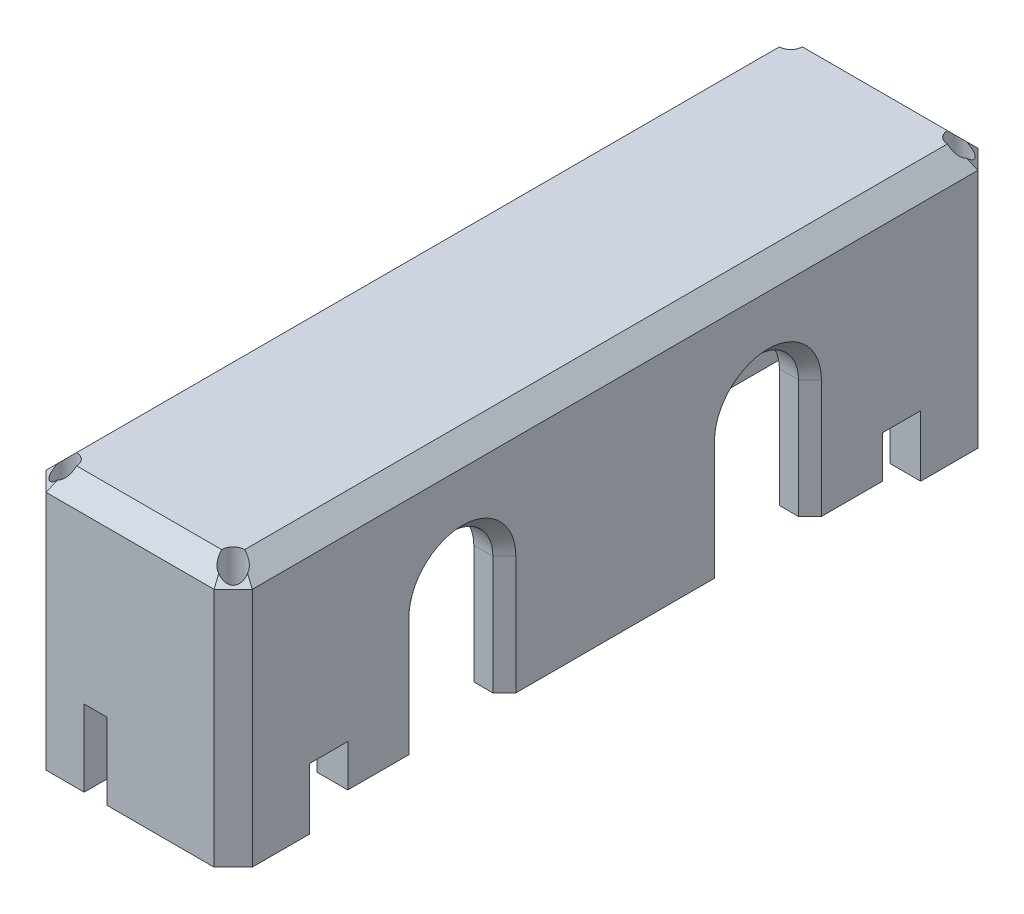
SolidWorks part; units mm, degrees
ref_plane "Płaszczyzna przednia" through (0, 0, 0) normal (0, 0, 1) x (1, 0, 0)
ref_plane "Płaszczyzna górna" through (0, 0, 0) normal (0, 1, 0) x (1, 0, 0)
ref_plane "Płaszczyzna prawa" through (0, 0, 0) normal (1, 0, 0) x (0, 0, -1)
sketch "Sketch2" plane through (0, 0, 0) normal (0, 1, 0) x (1, 0, 0)
  line L5 (27, -100) -> (-27, -100)
  line L6 (27, -100) -> (27, 100)
  line L11 (27, 100) -> (-27, 100)
  line L12 (-27, -100) -> (-27, 100)
  line L13 (27, -100) -> (-27, 100) construction
  line L14 (27, 100) -> (-27, -100) construction
  line L15 (19, -92) -> (-19, -92)
  line L16 (19, -92) -> (19, 92)
  line L17 (19, 92) -> (-19, 92)
  line L18 (-19, -92) -> (-19, 92)
  line L19 (19, -92) -> (-19, 92) construction
  line L20 (19, 92) -> (-19, -92) construction
  point P0 (0, 0)
  point P6 (0, 0)
  dimension "D1" = 8
  dimension "D2" = 8
  dimension "D3" = 200
  dimension "D4" = 54
extrude "Boss-Extrude2" add sketch "Sketch2" along normal blind 55
sketch "Sketch3" plane through (0, 0, 0) normal (1, 0, 0) x (0, 0, -1)
  line L0 (-40, 55) -> (-40, 0) construction
  line L1 (-100, 0) -> (100, 0) construction
  line L6 (-51, 0) -> (-51, 31)
  line L7 (-29, 0) -> (-29, 31)
  line L8 (-51, 0) -> (-29, 0)
  line L9 (0, 29.7) -> (0, -29.7) construction
  line L10 (51, 0) -> (51, 31)
  line L11 (29, 0) -> (29, 31)
  line L12 (51, 0) -> (29, 0)
  line L13 (-100, 55) -> (-100, 0) construction
  arc A0 (-51, 31) -> (-29, 31) centre (-40, 31) cw
  arc A1 (51, 31) -> (29, 31) centre (40, 31) ccw
  dimension "D1" = 60
  dimension "D3" = 11
  dimension "D4" = 31
extrude "Cut-Extrude1" cut sketch "Sketch3" along normal through all
sketch "Sketch5" plane through (0, 0, 0) normal (0, 1, 0) x (1, 0, 0)
  line L1 (27, 100) -> (-27, 100)
  line L2 (27, 100) -> (27, -100)
  line L3 (27, -100) -> (-27, -100)
  line L4 (-27, 100) -> (-27, -100)
  line L5 (27, 100) -> (-27, -100) construction
  line L6 (27, -100) -> (-27, 100) construction
  point P0 (0, 0)
extrude "Boss-Extrude3" add sketch "Sketch5" along normal blind 8 from surface starting at face at (0, 55, 0)
sketch "Sketch6" plane through (0, 0, 0) normal (0, 1, 0) x (1, 0, 0)
  line L1 (22, -95) -> (-22, -95) construction
  line L2 (22, -95) -> (22, 95) construction
  line L3 (22, 95) -> (-22, 95) construction
  line L4 (-22, -95) -> (-22, 95) construction
  line L5 (22, -95) -> (-22, 95) construction
  line L6 (22, 95) -> (-22, -95) construction
  line L7 (-27, -100) -> (27, -100) construction
  line L9 (-27, 100) -> (-27, -100) construction
  circle A0 centre (22, -95) radius 1.75
  circle A1 centre (-22, -95) radius 1.75
  circle A2 centre (-22, 95) radius 1.75
  circle A3 centre (22, 95) radius 1.75
  point P0 (0, 0)
  dimension "D3" = 3.5
  dimension "D1" = 5
  dimension "D2" = 5
extrude "Cut-Extrude2" cut sketch "Sketch6" along normal through all both and the other way through all
sketch "Sketch7" plane through (0, 0, 0) normal (0, 1, 0) x (1, 0, 0)
  circle A0 centre (-22, -95) radius 3
  circle A1 centre (-22, 95) radius 3
  circle A2 centre (22, 95) radius 3
  circle A3 centre (22, -95) radius 3
  dimension "D1" = 6
extrude "Cut-Extrude3" cut sketch "Sketch7" against normal blind 44 from surface starting at face at (22, 63, -93.25)
chamfer "Chamfer1" distance 5 angle 45 4 edges at (-27, 31.5, 100) (-27, 31.5, -100) (27, 31.5, -100) (27, 31.5, 100)
chamfer "Chamfer3" distance 5 angle 45 8 edges at (27, 63, 0) (24.5, 63, 97.5) (0, 63, 100) (-24.5, 63, 97.5) (-27, 63, 0) (-24.5, 63, -97.5) (0, 63, -100) (24.5, 63, -97.5)
chamfer "Chamfer4" distance 3 angle 45 6 edges at (27, 15.5, -29) (27, 42, -40) (27, 15.5, -51) (27, 15.5, 51) (27, 42, 40) (27, 15.5, 29)
sketch "Sketch8" plane through (0, 0, 0) normal (0, 1, 0) x (1, 0, 0)
  line L0 (27, -70) -> (19, -70)
  line L1 (27, -95) -> (27, -54) construction
  line L2 (19, -92) -> (19, 92) construction
  line L3 (19, -70) -> (19, -92)
  line L4 (19, -92) -> (-19, -92)
  line L5 (-19, -92) -> (-19, -70)
  line L6 (-19, 92) -> (-19, -92) construction
  line L7 (-19, -70) -> (-27, -70)
  line L8 (-27, 95) -> (-27, -95) construction
  line L9 (-27, -70) -> (-27, -95)
  line L10 (-27, -95) -> (-22, -100)
  line L11 (-22, -100) -> (22, -100)
  line L12 (22, -100) -> (27, -95)
  line L13 (27, -95) -> (27, -70)
  line L14 (-29.7, 0) -> (29.7, 0) construction
  line L15 (27, 95) -> (27, 70)
  line L16 (22, 100) -> (27, 95)
  line L17 (-22, 100) -> (22, 100)
  line L18 (-27, 95) -> (-22, 100)
  line L19 (-27, 70) -> (-27, 95)
  line L20 (-19, 70) -> (-27, 70)
  line L21 (-19, 92) -> (-19, 70)
  line L22 (19, 92) -> (-19, 92)
  line L23 (19, 70) -> (19, 92)
  line L24 (27, 70) -> (19, 70)
  circle A0 centre (22, -95) radius 1.75
  circle A1 centre (-22, -95) radius 1.75
  circle A2 centre (-22, 95) radius 1.75
  circle A3 centre (22, 95) radius 1.75
  dimension "D1" = 30
extrude "Boss-Extrude4" add sketch "Sketch8" against normal blind 5
sketch "Sketch9" plane through (0, 0, 0) normal (0, 0, 1) x (1, 0, 0)
  line L1 (-6, -5) -> (-12, -5)
  line L2 (-6, -5) -> (-6, 15)
  line L3 (-6, 15) -> (-12, 15)
  line L4 (-12, -5) -> (-12, 15)
  line L5 (-6, -5) -> (-12, 15) construction
  line L6 (-6, 15) -> (-12, -5) construction
  line L7 (-22, -5) -> (22, -5) construction
  point P0 (-9, 5)
  dimension "D1" = 20
  dimension "D2" = 6
  dimension "D3" = 6
extrude "Cut-Extrude4" cut sketch "Sketch9" against normal through all both and the other way through all
sketch "Sketch10" plane through (0, 0, 0) normal (1, 0, 0) x (0, 0, -1)
  line L0 (-70, -5) -> (-80, -5)
  line L1 (-70, -5) -> (-70, 11)
  line L2 (-80, -5) -> (-80, 11)
  line L3 (-70, 11) -> (-80, 11)
  line L4 (-70, -5) -> (-95, -5) construction
  line L5 (70, -5) -> (80, -5)
  line L6 (70, -5) -> (70, 11)
  line L7 (80, -5) -> (80, 11)
  line L8 (70, 11) -> (80, 11)
  line L9 (95, -5) -> (70, -5) construction
  dimension "D1" = 10
  dimension "D2" = 16
extrude "Cut-Extrude5" cut sketch "Sketch10" along normal through all
